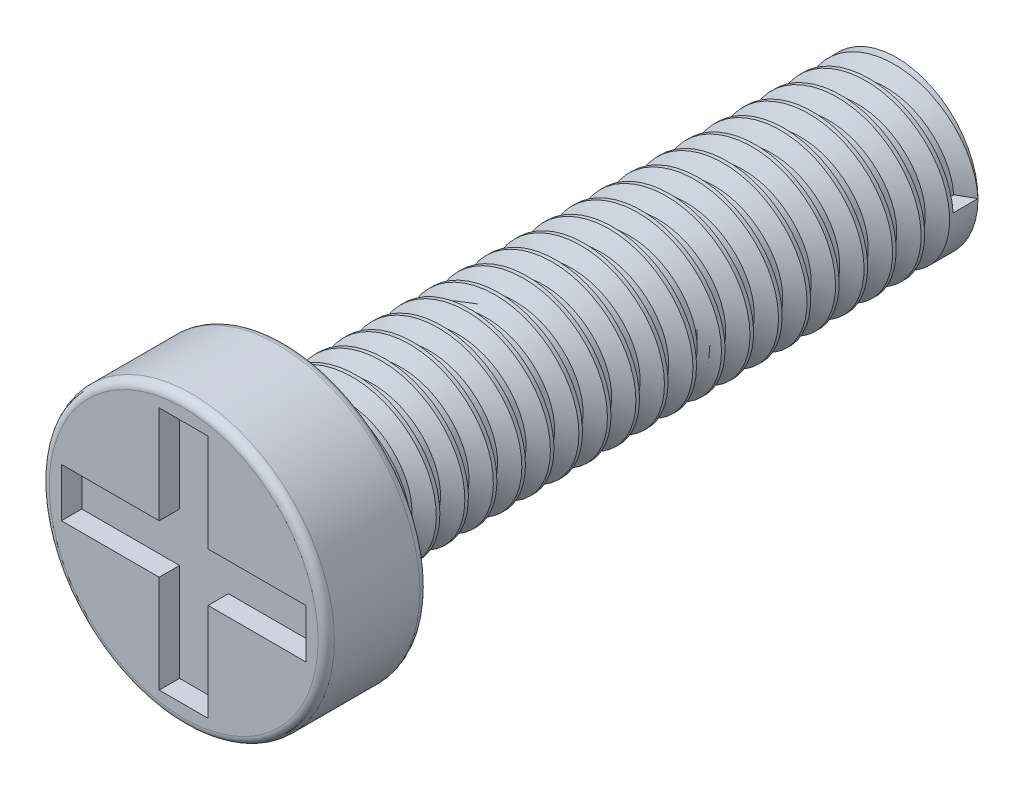
SolidWorks part; units mm, degrees
ref_plane "Front Plane" through (0, 0, 0) normal (0, 0, 1) x (1, 0, 0)
ref_plane "Top Plane" through (0, 0, 0) normal (0, 1, 0) x (1, 0, 0)
ref_plane "Right Plane" through (0, 0, 0) normal (1, 0, 0) x (0, 0, -1)
sketch "Sketch1" plane through (0, 0, 0) normal (0, 0, 1) x (1, 0, 0)
  circle A0 centre (0, 0) radius 2
  dimension "D1" = 4
extrude "Boss-Extrude1" add sketch "Sketch1" along normal blind 15
sketch "Sketch2" plane through (0, 0, 15) normal (0, 0, 1) x (1, 0, 0)
  circle A0 centre (0, 0) radius 3.5
  dimension "D1" = 7
extrude "Boss-Extrude2" add sketch "Sketch2" along normal blind 2.5
sketch "Sketch7" plane through (0, 0, 17.5) normal (0, 0, 1) x (1, 0, 0)
  line L1 (0.6, 3) -> (-0.6, 3)
  line L2 (0.6, 3) -> (0.6, -3)
  line L3 (0.6, -3) -> (-0.6, -3)
  line L4 (-0.6, 3) -> (-0.6, -3)
  line L5 (0, -3) -> (0, 3) construction
  line L6 (0.6, 0) -> (-0.6, 0) construction
  line L7 (3, -0.6) -> (-3, -0.6)
  line L8 (3, -0.6) -> (3, 0.6)
  line L9 (3, 0.6) -> (-3, 0.6)
  line L10 (-3, -0.6) -> (-3, 0.6)
  line L11 (0, 0.6) -> (0, -0.6) construction
  line L12 (3, 0) -> (-3, 0) construction
  point P0 (0, 0)
  point P4 (0, 0)
  dimension "D1" = 6
  dimension "D2" = 1.2
extrude "Cut-Extrude1" cut sketch "Sketch7" against normal blind 0.5 contours L9 L2 L1 L4 | L8 L9 L2 L7 | L2 L7 L4 L3 | L10 L7 L4 L9 | L2 L9 L4 L7
fillet "Fillet1" radius 0.2 2 edges at (3.5, 0, 17.5) (3.5, 0, 15)
thread "Thread1" pitch 0.7 start angle 0, offset 0, length 0, pitch 0.7, diameter 4
ref_plane "Plane1" through (2, 0, 0) normal (0, -1, 0) x (1, 0, 0)
sketch "Thread Profile1" plane through (2, 0, 0) normal (0, -1, 0) x (1, 0, 0)
  line L0 (0, 0) -> (0, 0.7) construction
  line L11 (0, 0) -> (0, 0.6125)
  line L12 (0, 0.6125) -> (-0.3789, 0.3937)
  line L13 (-0.3789, 0.3937) -> (-0.3789, 0.2187)
  line L15 (-0.3789, 0.2187) -> (0, 0)
  line L17 (-0.3789, 0.3062) -> (0, 0.3062) construction
  point P2 (0, 0)
  dimension "Pitch" = 0.7
  dimension "Profile_Angle" = 60
  dimension "Profile_Land" = 0.175
  dimension "Profile_Height" = 0.3789
